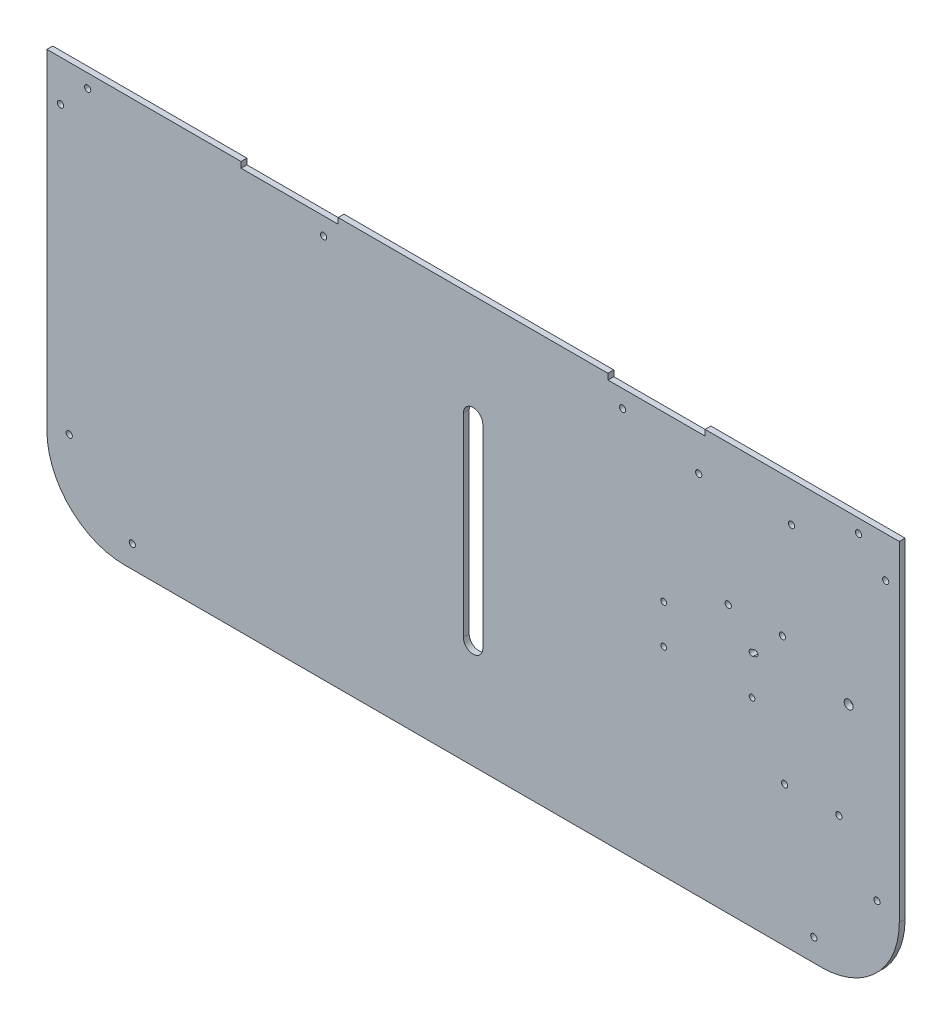
SolidWorks part; units mm, degrees
ref_plane "Plan de face" through (0, 0, 0) normal (0, 0, 1) x (1, 0, 0)
ref_plane "Plan de dessus" through (0, 0, 0) normal (0, 1, 0) x (1, 0, 0)
ref_plane "Plan de droite" through (0, 0, 0) normal (1, 0, 0) x (0, 0, -1)
sketch "Esquisse1" plane through (0, 0, 0) normal (0, 0, 1) x (1, 0, 0)
  line L1 (219.5, -105) -> (-219.5, -105)
  line L2 (219.5, -105) -> (219.5, 105)
  line L3 (219.5, 105) -> (-219.5, 105)
  line L4 (-219.5, -105) -> (-219.5, 105)
  line L5 (219.5, -105) -> (-219.5, 105) construction
  line L6 (219.5, 105) -> (-219.5, -105) construction
  point P0 (0, 0)
  dimension "D1" = 439
  dimension "D2" = 210
extrude "Boss.-Extru.1" add sketch "Esquisse1" along normal blind 3
sketch "Esquisse5" plane through (0, 0, 0) normal (0, 0, -1) x (-1, 0, 0)
  circle A0 centre (-145.2167, 18.0104) radius 1.4774
  circle A1 centre (-160.4356, -32.78) radius 1.5984
  circle A2 centre (-188.38, -32.79) radius 1.5875
  circle A3 centre (-193.46, 19.28) radius 2.3147
extrude "Enlèv. mat.-Extru.3" cut sketch "Esquisse5" against normal blind 4
sketch "Esquisse7" plane through (0, 0, 3) normal (0, 0, 1) x (1, 0, 0)
  line L0 (218.3793, -56.7403) -> (218.3793, -48.5264)
  line L1 (0, -159.4844) -> (0, 198.2871) construction
  line L2 (-217.5, -30.0053) -> (-249.9982, -30.0053) construction
  line L3 (219.5, -105) -> (219.5, 105) construction
  line L4 (217.5, -7.3773) -> (217.5, -52.6333) construction
  line L5 (217.5, -30.0053) -> (249.9982, -30.0053) construction
  line L6 (218.3793, -3.2704) -> (218.3793, -11.4842)
  line L7 (-217.5, -7.3773) -> (-217.5, -52.6333) construction
  line L8 (-218.3793, -3.2704) -> (-218.3793, -11.4842)
  line L9 (-218.3793, -56.7403) -> (-218.3793, -48.5264)
  line L10 (63.7, -103) -> (55.3, -103)
  line L11 (-63.7, -103) -> (-55.3, -103)
  line L12 (-219.5, -105) -> (219.5, -105) construction
  line L13 (-249.9982, 0) -> (281.4305, 0) construction
  line L14 (63.7, 103) -> (55.3, 103)
  line L15 (-63.7, 103) -> (-55.3, 103)
  line L16 (219.5, 74.5456) -> (0, 74.5456) construction
  line L17 (109.75, 74.5456) -> (109.75, 208.4684) construction
  line L18 (155.8, 103) -> (164.2, 103)
  line L19 (0, 74.5456) -> (-219.5, 74.5456) construction
  line L20 (-219.5, 105) -> (-219.5, -105) construction
  line L21 (-109.75, 74.5456) -> (-109.75, 208.4684) construction
  line L22 (-155.8, 103) -> (-164.2, 103)
  arc A0 (218.3793, -11.4842) -> (218.3793, -3.2704) centre (217.5, -7.3773) ccw
  arc A1 (218.3793, -48.5264) -> (218.3793, -56.7403) centre (217.5, -52.6333) cw
  arc A2 (-218.3793, -48.5264) -> (-218.3793, -56.7403) centre (-217.5, -52.6333) ccw
  arc A3 (-218.3793, -11.4842) -> (-218.3793, -3.2704) centre (-217.5, -7.3773) cw
  arc A4 (-55.3, -103) -> (-63.7, -103) centre (-59.5, -103) cw
  arc A5 (55.3, 103) -> (63.7, 103) centre (59.5, 103) cw
  arc A8 (-55.3, 103) -> (-63.7, 103) centre (-59.5, 103) ccw
  arc A10 (55.3, -103) -> (63.7, -103) centre (59.5, -103) ccw
  arc A11 (164.2, 103) -> (155.8, 103) centre (160, 103) ccw
  arc A12 (-164.2, 103) -> (-155.8, 103) centre (-160, 103) cw
  dimension "D1" = 4.2
  dimension "D2" = 2
  dimension "D3" = 4.2
  dimension "D5" = 4.2
  dimension "D6" = 2
  dimension "D7" = 160
  dimension "D4" = 2
extrude "Boss.-Extru.2" [suppressed] add sketch "Esquisse7" against normal through all
sketch "Esquisse9" [suppressed] plane through (0, 0, 3) normal (0, 0, 1) x (1, 0, 0)
  line L0 (0, -136.029) -> (0, 150.2761) construction
  circle A0 centre (59.5, -103) radius 1.6
  circle A1 centre (217.5, -52.6333) radius 1.6
  circle A2 centre (217.5, -7.3773) radius 1.6
  circle A3 centre (-217.5, -7.3773) radius 1.6
  circle A4 centre (-217.5, -52.6333) radius 1.6
  circle A5 centre (-59.5, -103) radius 1.6
  circle A6 centre (160, 103) radius 1.6
  circle A7 centre (59.5, 103) radius 1.6
  circle A8 centre (-59.5, 103) radius 1.6
  circle A9 centre (-160, 103) radius 1.6
  dimension "D1" = 3.2
  dimension "D2" = 3.2
  dimension "D3" = 3.2
  dimension "D4" = 3.2
  dimension "D5" = 3.2
  dimension "D6" = 3.2
  dimension "D7" = 3.2
extrude "Enlèv. mat.-Extru.4" [suppressed] cut sketch "Esquisse9" against normal through all
sketch "Esquisse10" plane through (0, 0, 3) normal (0, 0, 1) x (1, 0, 0)
  line L0 (219.5, 105) -> (-219.5, 105) construction
  line L1 (-119.5, 102) -> (-69.5, 102)
  line L2 (-119.5, 102) -> (-119.5, 105)
  line L3 (-119.5, 105) -> (-69.5, 105)
  line L4 (-69.5, 102) -> (-69.5, 105)
  line L5 (-69.5, 102) -> (-69.5, 105) construction
  line L6 (69.5, 102) -> (69.5, 105) construction
  line L7 (119.5, 102) -> (69.5, 102)
  line L8 (119.5, 102) -> (119.5, 105)
  line L9 (119.5, 105) -> (69.5, 105)
  line L10 (69.5, 102) -> (69.5, 105)
extrude "Enlèv. mat.-Extru.5" cut sketch "Esquisse10" against normal blind 4
sketch "Esquisse11" plane through (0, 0, 3) normal (0, 0, 1) x (1, 0, 0)
  line L0 (0, -50) -> (0, 50) construction
  line L1 (-5, -50) -> (-5, 50)
  line L2 (5, -50) -> (5, 50)
  arc A0 (-5, -50) -> (5, -50) centre (0, -50) ccw
  arc A1 (5, 50) -> (-5, 50) centre (0, 50) ccw
  point P3 (0, 0)
  point P8 (-5, 0)
  dimension "D2" = 5
  dimension "D1" = 100
extrude "Enlèv. mat.-Extru.6" cut sketch "Esquisse11" against normal through all
fillet "Fillet1" radius 40 2 edges at (219.5, -105, 1.5) (-219.5, -105, 1.5)
sketch "Sketch1" plane through (0, 0, 0) normal (0, 0, -1) x (-1, 0, 0)
  circle A0 centre (-208, -61) radius 1.6
extrude "Cut-Extrude1" cut sketch "Sketch1" against normal through all
sketch "Sketch2" plane through (0, 0, 0) normal (0, 0, -1) x (-1, 0, 0)
  circle A0 centre (208, -61) radius 1.6
  circle A1 centre (175.5, -93.5) radius 1.6
  point P6 (175.5, -93.5)
  point P8 (208, -61)
extrude "Cut-Extrude2" cut sketch "Sketch2" against normal through all
sketch "Sketch3" plane through (0, 0, 0) normal (0, 0, -1) x (-1, 0, 0)
  circle A0 centre (-175.5, -93.5) radius 1.6
  point P3 (-175.5, -93.5)
extrude "Cut-Extrude3" cut sketch "Sketch3" against normal through all
sketch "Sketch4" plane through (0, 0, 0) normal (0, 0, -1) x (-1, 0, 0)
  circle A0 centre (-198.5, 98) radius 1.6
  circle A1 centre (-212.5, 84) radius 1.6
  circle A2 centre (198.5, 98) radius 1.6
  circle A3 centre (212.5, 84) radius 1.6
extrude "Cut-Extrude4" cut sketch "Sketch4" against normal through all
sketch "Sketch5" plane through (0, 0, 0) normal (0, 0, -1) x (-1, 0, 0)
  circle A0 centre (77, 93) radius 1.6
  circle A1 centre (-77, 93) radius 1.6
extrude "Cut-Extrude5" cut sketch "Sketch5" against normal through all
sketch "Sketch7" plane through (0, 0, 0) normal (0, 0, -1) x (-1, 0, 0)
  circle A0 centre (-131.4, 32.8) radius 1.6
  circle A1 centre (-159.3, 32.8) radius 1.6
  circle A2 centre (-116.2, 83.6) radius 1.6
  circle A3 centre (-164, 84.7) radius 1.6
  dimension "D1" = 3.2
extrude "Cut-Extrude6" cut sketch "Sketch7" against normal through all
sketch "Sketch8" plane through (0, 0, 0) normal (0, 0, -1) x (-1, 0, 0)
  circle A0 centre (-98.175, -2.55) radius 1.475
  circle A1 centre (-98.175, 17.45) radius 1.475
  circle A2 centre (-143.675, 17.45) radius 1.475
  circle A3 centre (-143.675, -2.55) radius 1.475
extrude "Cut-Extrude7" cut sketch "Sketch8" against normal through all
